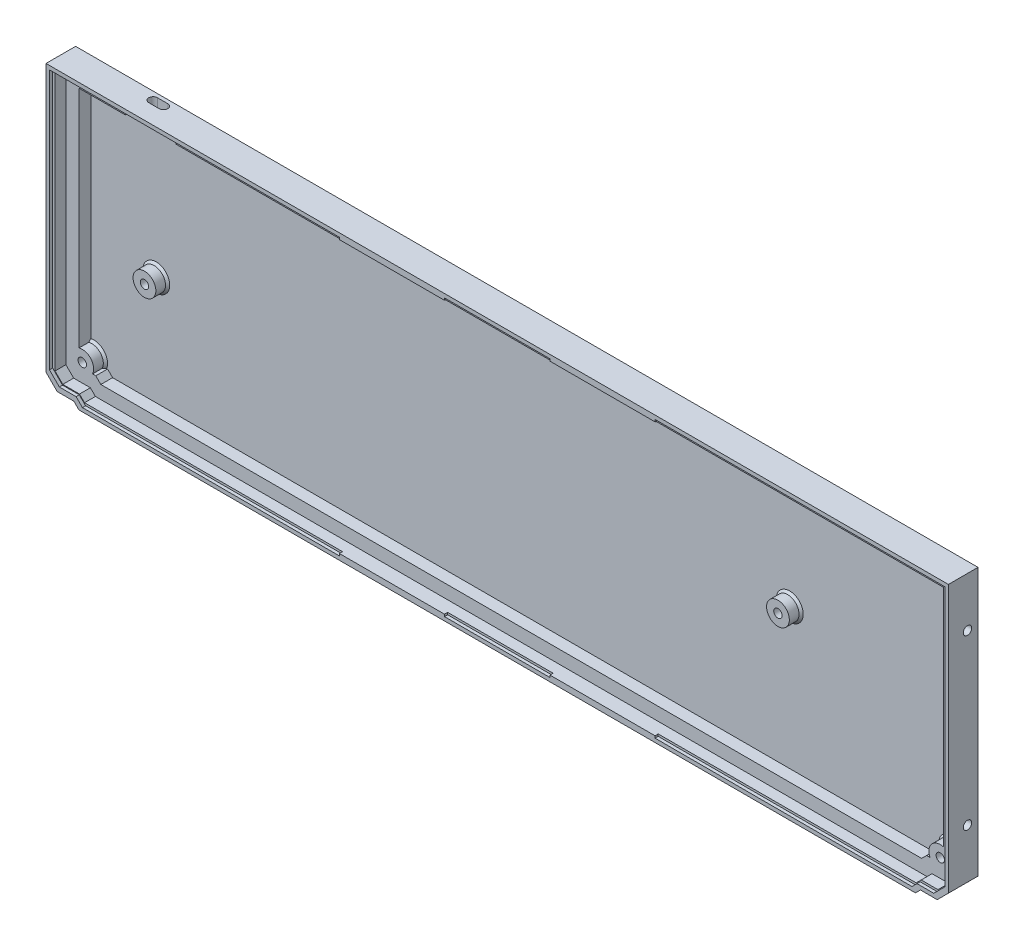
SolidWorks part; units mm, degrees
ref_plane "Přední rovina" through (0, 0, 0) normal (0, 0, 1) x (1, 0, 0)
ref_plane "Horní rovina" through (0, 0, 0) normal (0, 1, 0) x (1, 0, 0)
ref_plane "Pravá rovina" through (0, 0, 0) normal (1, 0, 0) x (0, 0, -1)
sketch "Skica3" plane through (0, 0, 0) normal (0, 0, 1) x (1, 0, 0)
  line L0 (0, 0) -> (415.1053, 0) construction
  line L1 (415.1053, 0) -> (416.6927, -1.5875) construction
  line L2 (416.6927, -1.5875) -> (416.6927, -119.8485) construction
  line L3 (0, 0) -> (-1.5875, -1.5875) construction
  line L4 (-1.5875, -1.5875) -> (-1.5875, -119.8485) construction
  line L5 (-1.5875, -119.8485) -> (0.7934, -122.2292) construction
  line L6 (0.7934, -122.2292) -> (8.7304, -122.2292) construction
  line L7 (8.7304, -122.2292) -> (11.1113, -124.61) construction
  line L8 (11.1113, -124.61) -> (403.9933, -124.61) construction
  line L9 (403.9933, -124.61) -> (406.3744, -122.2294) construction
  line L10 (406.3744, -122.2294) -> (414.3114, -122.2294) construction
  line L11 (416.6927, -119.8485) -> (414.3114, -122.2294) construction
  line L12 (2.4125, -4) -> (412.6927, -4)
  line L13 (412.6927, -4) -> (412.6927, -4)
  line L14 (412.6927, -4) -> (412.6927, -118.1914)
  line L15 (412.6927, -118.1914) -> (412.6547, -118.2294)
  line L16 (404.7177, -118.2294) -> (412.6547, -118.2294)
  line L17 (402.3367, -120.61) -> (404.7177, -118.2294)
  line L18 (12.7681, -120.61) -> (402.3367, -120.61)
  line L19 (10.3872, -118.2292) -> (12.7681, -120.61)
  line L20 (2.4502, -118.2292) -> (10.3872, -118.2292)
  line L21 (2.4125, -118.1915) -> (2.4502, -118.2292)
  line L22 (2.4125, -4) -> (2.4125, -118.1915)
  line L23 (2.4125, -4) -> (2.4125, -4)
  line L24 (-1.5875, -119.8485) -> (415.1053, 0) construction
  line L26 (0, 0) -> (416.6927, -119.8485) construction
  dimension "D1" = 135
  dimension "D2" = 135
  dimension "D3" = 4
  dimension "D4" = 2.245
  dimension "D5" = 2.245
  dimension "D6" = 118.261
  dimension "D7" = 118.261
  dimension "D8" = 3.367
  dimension "D9" = 7.937
  dimension "D10" = 3.367
  dimension "D11" = 392.882
  dimension "D12" = 3.367
  dimension "D13" = 7.937
  dimension "D14" = 3.3674
extrude "Přidat vysunutím1" add sketch "Skica3" along normal blind 5.6
shell "Skořepina1" thickness 1.8 removed face at (207.5525, -95.852, 5.6) outward yes
sketch "Skica7" plane through (0, 0, 5.6) normal (0, 0, 1) x (1, 0, 0)
  line L20 (-6.5875, 5) -> (-6.5875, -121.9196)
  line L21 (-6.5875, -121.9196) -> (-1.2775, -127.2292)
  line L22 (-1.2775, -127.2292) -> (6.6595, -127.2292)
  line L23 (6.6595, -127.2292) -> (9.0403, -129.61)
  line L24 (9.0403, -129.61) -> (406.0641, -129.61)
  line L25 (406.0641, -129.61) -> (408.4452, -127.2294)
  line L26 (408.4452, -127.2294) -> (416.3822, -127.2294)
  line L27 (416.3822, -127.2294) -> (421.6927, -121.9198)
  line L28 (421.6927, -121.9198) -> (421.6927, 5)
  line L29 (421.6927, 5) -> (-6.5875, 5)
  line L30 (-6.5875, 5) -> (-6.5875, -121.9196)
  line L31 (-6.5875, -121.9196) -> (-1.2775, -127.2292)
  line L32 (-1.2775, -127.2292) -> (6.6595, -127.2292)
  line L33 (6.6595, -127.2292) -> (9.0403, -129.61)
  line L34 (9.0403, -129.61) -> (406.0641, -129.61)
  line L35 (406.0641, -129.61) -> (408.4452, -127.2294)
  line L36 (408.4452, -127.2294) -> (416.3822, -127.2294)
  line L37 (416.3822, -127.2294) -> (421.6927, -121.9198)
  line L38 (421.6927, -121.9198) -> (421.6927, 5)
  line L39 (421.6927, 5) -> (-6.5875, 5)
  line L40 (-3.7875, 2.2) -> (-3.7875, -120.7598)
  line L41 (-3.7875, -120.7598) -> (-0.1178, -124.4292)
  line L42 (-0.1178, -124.4292) -> (7.8192, -124.4292)
  line L43 (7.8192, -124.4292) -> (10.2001, -126.81)
  line L44 (10.2001, -126.81) -> (404.9045, -126.81)
  line L45 (404.9045, -126.81) -> (407.2855, -124.4294)
  line L46 (407.2855, -124.4294) -> (415.2225, -124.4294)
  line L47 (415.2225, -124.4294) -> (418.8927, -120.7598)
  line L48 (418.8927, -120.7598) -> (418.8927, 2.2)
  line L49 (418.8927, 2.2) -> (-3.7875, 2.2)
  line L50 (-3.7875, 2.2) -> (-3.7875, -120.7598)
  line L51 (-3.7875, -120.7598) -> (-0.1178, -124.4292)
  line L52 (-0.1178, -124.4292) -> (7.8192, -124.4292)
  line L53 (7.8192, -124.4292) -> (10.2001, -126.81)
  line L54 (10.2001, -126.81) -> (404.9045, -126.81)
  line L55 (404.9045, -126.81) -> (407.2855, -124.4294)
  line L56 (407.2855, -124.4294) -> (415.2225, -124.4294)
  line L57 (415.2225, -124.4294) -> (418.8927, -120.7598)
  line L58 (418.8927, -120.7598) -> (418.8927, 2.2)
  line L59 (418.8927, 2.2) -> (-3.7875, 2.2)
  dimension "D2" = 4.4
  dimension "D1" = 7.2
extrude "Přidat vysunutím3" add sketch "Skica7" along normal blind 5.15 separate body
sketch "Skica8" plane through (0, 0, 5.6) normal (0, 0, -1) x (-1, 0, 0)
  line L0 (-421.6927, 5) -> (6.5875, 5)
  line L1 (6.5875, 5) -> (6.5875, -121.9196)
  line L2 (6.5875, 5) -> (6.5875, -121.9196) construction
  line L3 (6.5875, -121.9196) -> (1.2775, -127.2292)
  line L4 (1.2775, -127.2292) -> (-6.6595, -127.2292)
  line L5 (-6.6595, -127.2292) -> (-9.0403, -129.61)
  line L6 (-9.0403, -129.61) -> (-406.0641, -129.61)
  line L7 (-406.0641, -129.61) -> (-408.4452, -127.2294)
  line L8 (-408.4452, -127.2294) -> (-416.3822, -127.2294)
  line L9 (-416.3822, -127.2294) -> (-421.6927, -121.9198)
  line L10 (-421.6927, -121.9198) -> (-421.6927, 5)
  line L11 (-0.6125, -2.2) -> (-0.6125, -118.9371)
  line L12 (-414.4927, -2.2) -> (-0.6125, -2.2) construction
  line L13 (-0.6125, -2.2) -> (-0.6125, -118.9371) construction
  line L14 (-0.6125, -118.9371) -> (-1.7047, -120.0292)
  line L15 (-1.7047, -120.0292) -> (-9.6417, -120.0292)
  line L16 (-9.6417, -120.0292) -> (-12.0226, -122.41)
  line L17 (-12.0226, -122.41) -> (-403.0822, -122.41)
  line L18 (-403.0822, -122.41) -> (-405.4632, -120.0294)
  line L19 (-405.4632, -120.0294) -> (-413.4002, -120.0294) construction
  line L20 (-405.4632, -120.0294) -> (-413.4002, -120.0294)
  line L21 (-413.4002, -120.0294) -> (-414.4927, -118.9371) construction
  line L22 (-413.4002, -120.0294) -> (-414.4927, -118.9371)
  line L23 (-414.4927, -118.9371) -> (-414.4927, -2.2)
  line L24 (-414.4927, -2.2) -> (-0.6125, -2.2)
extrude "Přidat vysunutím4" add sketch "Skica8" along normal up to surface (7.4 mm away) up to face at (207.5525, -96.7211, -1.8)
sketch "Skica11" plane through (0, 0, 10.75) normal (0, 0, 1) x (1, 0, 0)
  line L0 (207.5526, 3.195) -> (207.5526, 5) construction
  line L1 (421.6927, 5) -> (-6.5875, 5) construction
  line L2 (207.5522, -127.805) -> (207.5522, -129.61) construction
  line L3 (9.0403, -129.61) -> (406.0641, -129.61) construction
  line L4 (-4.9474, -58.4598) -> (-6.5875, -58.4598) construction
  line L5 (-6.5875, 5) -> (-6.5875, -121.9196) construction
  line L6 (420.0526, -58.4599) -> (421.6927, -58.4599) construction
  line L7 (421.6927, -121.9198) -> (421.6927, 5) construction
  line L8 (404.9045, -126.81) -> (407.2855, -124.4294) construction
  line L9 (415.2225, -124.4294) -> (418.8927, -120.7598) construction
  line L10 (7.8192, -124.4292) -> (10.2001, -126.81) construction
  line L11 (-3.7875, -120.7598) -> (-0.1178, -124.4292) construction
  line L13 (407.2855, -124.4294) -> (415.2225, -124.4294) construction
  line L14 (-0.1178, -124.4292) -> (7.8192, -124.4292) construction
  line L30 (420.0526, 3.195) -> (-4.9474, 3.195)
  line L31 (-4.9474, 3.195) -> (-4.9474, -120.1146)
  line L32 (-4.9474, -120.1146) -> (-0.24, -124.8217)
  line L33 (-0.24, -124.8217) -> (7.697, -124.8217)
  line L34 (7.697, -124.8217) -> (10.6804, -127.805)
  line L35 (10.6804, -127.805) -> (404.4241, -127.805)
  line L36 (404.4241, -127.805) -> (406.8051, -125.4244)
  line L37 (406.8051, -125.4244) -> (414.7421, -125.4244)
  line L38 (414.7421, -125.4244) -> (420.0526, -120.1148)
  line L39 (420.0526, -120.1148) -> (420.0526, 3.195)
  line L45 (421.6927, 5) -> (-6.5875, 5)
  line L46 (-6.5875, 5) -> (-6.5875, -121.9196)
  line L47 (-6.5875, -121.9196) -> (-1.2775, -127.2292)
  line L48 (-1.2775, -127.2292) -> (6.6595, -127.2292)
  line L49 (6.6595, -127.2292) -> (9.0403, -129.61)
  line L50 (9.0403, -129.61) -> (406.0641, -129.61)
  line L51 (406.0641, -129.61) -> (408.4452, -127.2294)
  line L52 (408.4452, -127.2294) -> (416.3822, -127.2294)
  line L53 (416.3822, -127.2294) -> (421.6927, -121.9198)
  line L54 (421.6927, -121.9198) -> (421.6927, 5)
  line L55 (421.6927, 5) -> (-6.5875, 5)
  line L56 (-6.5875, 5) -> (-6.5875, -121.9196)
  line L57 (-6.5875, -121.9196) -> (-1.2775, -127.2292)
  line L58 (-1.2775, -127.2292) -> (6.6595, -127.2292)
  line L59 (6.6595, -127.2292) -> (9.0403, -129.61)
  line L60 (9.0403, -129.61) -> (406.0641, -129.61)
  line L61 (406.0641, -129.61) -> (408.4452, -127.2294)
  line L62 (408.4452, -127.2294) -> (416.3822, -127.2294)
  line L63 (416.3822, -127.2294) -> (421.6927, -121.9198)
  line L64 (421.6927, -121.9198) -> (421.6927, 5)
  point P0 (207.5523, -63.11)
  point P2 (207.5523, -63.11)
  dimension "D1" = 131
  dimension "D2" = 425
  dimension "D3" = 0
extrude "Přidat vysunutím5" add sketch "Skica11" along normal blind 1.5
sketch "Skica14" plane through (0, 0, 10.75) normal (0, 0, 1) x (1, 0, 0)
  line L0 (418.8927, 2.2) -> (-3.7875, 2.2) construction
  line L1 (182.5326, 2.2) -> (132.6326, 2.2)
  line L2 (182.5326, 2.2) -> (182.5326, 3.195)
  line L3 (182.5326, 3.195) -> (132.6326, 3.195)
  line L4 (132.6326, 2.2) -> (132.6326, 3.195)
  line L5 (420.0526, 3.195) -> (-4.9474, 3.195) construction
  line L6 (418.8927, 2.2) -> (-3.7875, 2.2) construction
  line L7 (232.5726, 2.2) -> (282.4726, 2.2)
  line L8 (232.5726, 2.2) -> (232.5726, 3.195)
  line L9 (232.5726, 3.195) -> (282.4726, 3.195)
  line L10 (282.4726, 2.2) -> (282.4726, 3.195)
  line L11 (207.5526, 3.195) -> (207.5522, -127.805) construction
  line L12 (10.6804, -127.805) -> (404.4241, -127.805) construction
  line L13 (10.2001, -126.81) -> (404.9045, -126.81) construction
  line L14 (232.5722, -126.81) -> (282.4722, -126.81)
  line L15 (232.5722, -126.81) -> (232.5722, -127.805)
  line L16 (232.5722, -127.805) -> (282.4722, -127.805)
  line L17 (282.4722, -126.81) -> (282.4722, -127.805)
  line L18 (10.6804, -127.805) -> (404.4241, -127.805) construction
  line L20 (182.5322, -126.81) -> (132.6322, -126.81)
  line L21 (182.5322, -126.81) -> (182.5322, -127.805)
  line L22 (182.5322, -127.805) -> (132.6322, -127.805)
  line L23 (132.6322, -126.81) -> (132.6322, -127.805)
  dimension "D1" = 49.9
  dimension "D2" = 49.9
  dimension "D3" = 25.02
  dimension "D4" = 25.02
  dimension "D5" = 49.9
  dimension "D6" = 49.9
  dimension "D7" = 25.02
  dimension "D8" = 25.02
extrude "Přidat vysunutím6" add sketch "Skica14" along normal up to surface (1.5 mm away) up to face at (207.5524, -100.1977, 12.25)
sketch "Skica15" plane through (0, 0, 0) normal (0, 0, 1) x (1, 0, 0)
  line L1 (34.9015, 4.5) -> (37.9015, 4.5)
  line L2 (34.9015, 4.5) -> (34.9015, -4.5)
  line L3 (34.9015, -4.5) -> (37.9015, -4.5)
  line L4 (37.9015, 4.5) -> (37.9015, -4.5)
  line L5 (34.9015, 4.5) -> (37.9015, -4.5) construction
  line L6 (34.9015, -4.5) -> (37.9015, 4.5) construction
  line L20 (-1.5875, 0) -> (-1.5875, -119.8485)
  line L21 (-1.5875, -119.8485) -> (0.7934, -122.2292)
  line L22 (0.7934, -122.2292) -> (8.7304, -122.2292)
  line L23 (8.7304, -122.2292) -> (11.1113, -124.61)
  line L24 (11.1113, -124.61) -> (403.9933, -124.61)
  line L25 (403.9933, -124.61) -> (406.3744, -122.2294)
  line L26 (406.3744, -122.2294) -> (414.3114, -122.2294)
  line L27 (414.3114, -122.2294) -> (416.6927, -119.8485)
  line L28 (416.6927, -119.8485) -> (416.6927, 0)
  line L29 (416.6927, 0) -> (-1.5875, 0)
  line L30 (-1.5875, 0) -> (-1.5875, -119.8485) construction
  line L31 (-1.5875, -119.8485) -> (0.7934, -122.2292) construction
  line L32 (0.7934, -122.2292) -> (8.7304, -122.2292) construction
  line L33 (8.7304, -122.2292) -> (11.1113, -124.61) construction
  line L34 (11.1113, -124.61) -> (403.9933, -124.61) construction
  line L35 (403.9933, -124.61) -> (406.3744, -122.2294) construction
  line L36 (406.3744, -122.2294) -> (414.3114, -122.2294) construction
  line L37 (414.3114, -122.2294) -> (416.6927, -119.8485) construction
  line L38 (416.6927, -119.8485) -> (416.6927, 0) construction
  line L39 (416.6927, 0) -> (-1.5875, 0) construction
  circle A0 centre (3.9685, -115.9542) radius 5.4
  circle A1 centre (33.4915, -69.051) radius 5.4
  circle A2 centre (411.1977, -115.8794) radius 5.4
  circle A3 centre (334.1477, -53.972) radius 5.4
  point P2 (-1.4315, -115.9542)
  point P3 (3.9685, -121.3542)
  point P4 (28.0915, -69.051)
  point P8 (33.4915, -74.451)
  point P12 (411.1977, -121.2794)
  point P13 (416.5977, -115.8794)
  point P17 (334.1477, -48.572)
  point P19 (339.5477, -53.972)
  point P21 (36.4015, 0)
  point P23 (36.4015, 0)
  dimension "D2" = 0.156
  dimension "D4" = 10.8
  dimension "D7" = 10.8
  dimension "D10" = 10.8
  dimension "D13" = 10.8
  dimension "D3" = 0.875
  dimension "D5" = 29.679
  dimension "D6" = 50.159
  dimension "D8" = 0.095
  dimension "D9" = 0.95
  dimension "D11" = 77.145
  dimension "D12" = 48.572
  dimension "D14" = 37.989
  dimension "D15" = 9
  dimension "D16" = 3
  dimension "D1" = 4
extrude "Přidat vysunutím7" add sketch "Skica15" along normal blind 5.6
sketch "Skica16" plane through (0, 0, 5.6) normal (0, 0, 1) x (1, 0, 0)
  circle A0 centre (3.9685, -115.9542) radius 2
  circle A1 centre (33.4915, -69.051) radius 2
  circle A2 centre (334.1477, -53.972) radius 2
  circle A3 centre (411.1977, -115.8794) radius 2
  dimension "D1" = 4
  dimension "D2" = 4
  dimension "D3" = 4
  dimension "D4" = 4
extrude "Odebrat vysunutím1" cut sketch "Skica16" against normal blind 5.75
chamfer "Zkosení1" distance 1 angle 45 4 edges at (407.0694, -112.3984, 0) (8.0492, -112.4175, 0) (38.8915, -69.051, 0) (339.5477, -53.972, 0)
sketch "Skica17" plane through (0, 0, 5.6) normal (0, 0, 1) x (1, 0, 0)
  line L0 (34.9015, -4.5) -> (37.9015, -4.5) construction
  line L1 (24.4015, -11.2) -> (48.4015, -11.2)
  line L2 (24.4015, -11.2) -> (24.4015, 2.2)
  line L3 (24.4015, 2.2) -> (48.4015, 2.2)
  line L4 (48.4015, -11.2) -> (48.4015, 2.2)
  line L5 (24.4015, -11.2) -> (48.4015, 2.2) construction
  line L6 (24.4015, 2.2) -> (48.4015, -11.2) construction
  line L7 (418.8927, 2.2) -> (-3.7875, 2.2) construction
  point P0 (36.4015, -4.5)
  dimension "D1" = 24
extrude "Odebrat vysunutím2" cut sketch "Skica17" against normal blind 1.6
sketch "Skica18" plane through (0, -4.5, 0) normal (0, -1, 0) x (1, 0, 0)
  line L0 (33.9515, 1.95) -> (38.8515, 1.95) construction
  line L3 (33.9515, 4) -> (38.8515, 4)
  line L4 (33.9515, -0.1) -> (38.8515, -0.1)
  line L5 (36.4015, 4) -> (36.4015, 1.95) construction
  line L6 (37.9015, 4) -> (34.9015, 4) construction
  arc A0 (33.9515, 4) -> (33.9515, -0.1) centre (33.9515, 1.95) ccw
  arc A1 (38.8515, -0.1) -> (38.8515, 4) centre (38.8515, 1.95) ccw
  point P6 (36.4015, 1.95)
  point P11 (31.9015, 1.95)
  point P12 (40.9015, 1.95)
  dimension "D1" = 9
  dimension "D2" = 4.1
  dimension "D3" = 2.05
extrude "Odebrat vysunutím3" cut sketch "Skica18" against normal up to surface (9.5 mm away) up to face at (207.5526, 5, 5.225)
sketch "Skica23" plane through (-6.5875, 0, 0) normal (-1, 0, 0) x (0, 0, 1)
  line L2 (-1.8, 5) -> (-1.8, -121.9196) construction
  line L4 (-1.8, -58.4598) -> (12.25, -58.4598) construction
  line L5 (12.25, 5) -> (12.25, -121.9196) construction
  circle A0 centre (3.2, -18.4598) radius 2
  circle A1 centre (3.2, -98.4598) radius 2
  point P8 (-1.8, -58.4598)
  dimension "D2" = 4
  dimension "D3" = 4
  dimension "D1" = 40
  dimension "D4" = 5
extrude "Odebrat vysunutím4" cut sketch "Skica23" against normal blind 5.7
sketch "Skica24" plane through (421.6927, 0, 0) normal (1, 0, 0) x (0, 0, -1)
  line L0 (1.8, -58.4599) -> (-12.25, -58.4599) construction
  line L1 (1.8, -121.9198) -> (1.8, 5) construction
  line L2 (-12.25, -121.9198) -> (-12.25, 5) construction
  circle A0 centre (-3.2, -18.4599) radius 2
  circle A1 centre (-3.2, -98.4599) radius 2
  dimension "D1" = 4
  dimension "D2" = 4
  dimension "D3" = 40
  dimension "D4" = 5
extrude "Odebrat vysunutím5" cut sketch "Skica24" against normal blind 5.7
sketch "Skica25" plane through (0, 0, -1.8) normal (0, 0, -1) x (-1, 0, 0)
  line L0 (-421.6927, -121.9198) -> (-421.6927, 5) construction
  line L1 (-421.6927, 5) -> (6.5875, 5) construction
  line L2 (6.5875, 5) -> (6.5875, -121.9196) construction
  line L3 (-9.0403, -129.61) -> (-406.0641, -129.61) construction
  circle A0 centre (-401.6927, -15) radius 6.25
  circle A1 centre (-13.4125, -15) radius 6.25
  circle A2 centre (-388.4452, -109.61) radius 6.25
  circle A3 centre (-26.6595, -109.61) radius 6.25
  dimension "D1" = 12.5
  dimension "D2" = 12.5
  dimension "D3" = 12.5
  dimension "D4" = 12.5
  dimension "D5" = 20
  dimension "D6" = 20
  dimension "D7" = 20
  dimension "D8" = 20
  dimension "D9" = 20
  dimension "D10" = 20
  dimension "D11" = 20
  dimension "D12" = 20
extrude "Odebrat vysunutím6" cut sketch "Skica25" against normal blind 1.5
